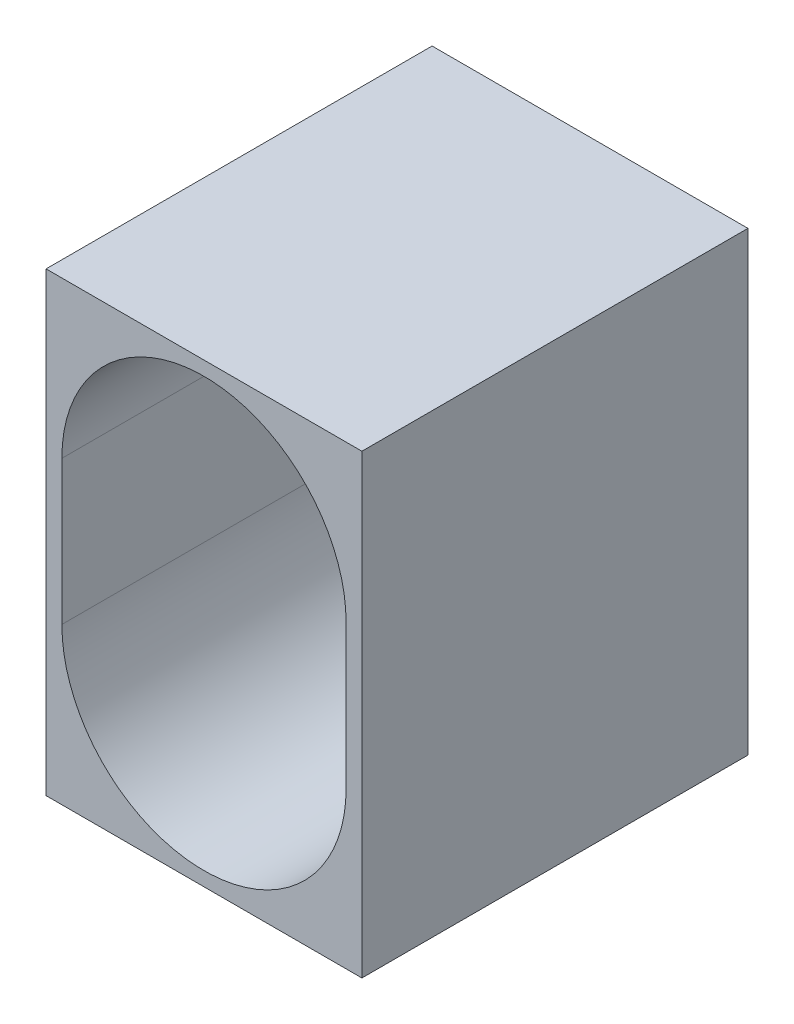
SolidWorks part; units mm, degrees
material "6061 Alloy"
ref_plane "Front Plane" through (0, 0, 0) normal (0, 0, 1) x (1, 0, 0)
ref_plane "Top Plane" through (0, 0, 0) normal (0, 1, 0) x (1, 0, 0)
ref_plane "Right Plane" through (0, 0, 0) normal (1, 0, 0) x (0, 0, -1)
sketch "Sketch4" plane through (0, 0, 0) normal (0, 0, 1) x (1, 0, 0)
  line L1 (-30.2849, 20.5607) -> (14.7151, 20.5607)
  line L2 (-30.2849, 20.5607) -> (-30.2849, -44.4393)
  line L3 (-30.2849, -44.4393) -> (14.7151, -44.4393)
  line L4 (14.7151, 20.5607) -> (14.7151, -44.4393)
  dimension "D1" = 45
  dimension "D2" = 65
extrude "Boss-Extrude2" add sketch "Sketch4" along normal blind 55
sketch "Sketch5" plane through (0, 0, 55) normal (0, 0, 1) x (1, 0, 0)
  line L0 (-7.7849, -22.1893) -> (-7.7849, -1.6893) construction
  line L1 (-21.0349, -22.1893) -> (-21.0349, -1.6893) construction
  line L2 (5.4651, -22.1893) -> (5.4651, -1.6893) construction
  line L3 (-30.2849, -44.4393) -> (14.7151, -44.4393) construction
  line L4 (-30.2849, 20.5607) -> (-30.2849, -44.4393) construction
  line L5 (-28.0349, -22.1893) -> (-28.0349, -1.6893)
  line L6 (12.4651, -22.1893) -> (12.4651, -1.6893)
  arc A0 (-21.0349, -22.1893) -> (5.4651, -22.1893) centre (-7.7849, -22.1893) ccw construction
  arc A1 (5.4651, -1.6893) -> (-21.0349, -1.6893) centre (-7.7849, -1.6893) ccw construction
  arc A2 (12.4651, -1.6893) -> (-28.0349, -1.6893) centre (-7.7849, -1.6893) ccw
  arc A3 (-28.0349, -22.1893) -> (12.4651, -22.1893) centre (-7.7849, -22.1893) ccw
  point P2 (-7.7849, -11.9393)
  dimension "D3" = 7
  dimension "D1" = 32.5
  dimension "D2" = 22.5
extrude "Cut-Extrude1" cut sketch "Sketch5" against normal blind 52.5
hole_wizard "1/4-28 Tapped Hole1" positions "Sketch6" profile "Sketch7" tap size "1/4-28" standard "ANSI Inch" end condition up to next
sketch "Sketch6" plane through (0, 0, 0) normal (0, 0, -1) x (-1, 0, 0)
  line L0 (-14.7151, -44.4393) -> (-14.7151, 20.5607) construction
  line L1 (-14.7151, 20.5607) -> (30.2849, 20.5607) construction
  point P0 (7.7849, -16.4393)
  dimension "D1" = 22.5
  dimension "D2" = 37
sketch "Sketch7" plane through (-7.7849, -16.4393, 0) normal (1, 0, 0) x (0, 1, 0)
  line L0 (0, 0) -> (0, 2.5)
  line L1 (0, 2.5) -> (2.7051, 2.5)
  line L2 (2.7051, 2.5) -> (2.7051, 0)
  line L5 (2.7051, 0) -> (0, 0)
  line L11 (0, -6.35) -> (0, 107.95) construction
  dimension "Thru Tap Drill Dia." = 5.4102
  dimension "Thru Tap Drill Depth" = 2.5
cosmetic thread "Hole Thread1"
